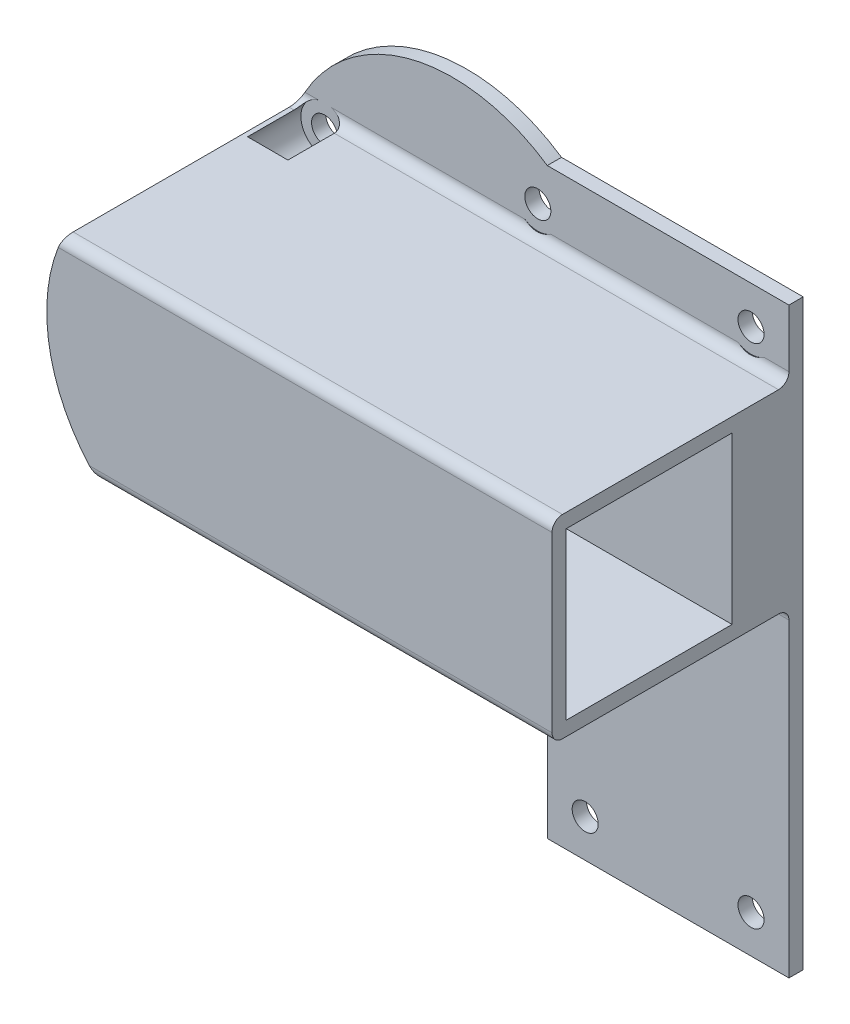
SolidWorks part; units mm, degrees
ref_plane "Front Plane" through (0, 0, 0) normal (0, 0, 1) x (1, 0, 0)
ref_plane "Top Plane" through (0, 0, 0) normal (0, 1, 0) x (1, 0, 0)
ref_plane "Right Plane" through (0, 0, 0) normal (1, 0, 0) x (0, 0, -1)
sketch "Sketch1" plane through (0, 0, 0) normal (0, 0, 1) x (1, 0, 0)
  line L0 (-35, -107) -> (0, -107) construction
  line L1 (-90, -9) -> (-90, -34) construction
  line L5 (8, 8) -> (-43, 8)
  line L6 (8, 8) -> (8, -115)
  line L7 (8, -115) -> (-43, -115)
  line L8 (-43, 8) -> (-43, -1.8875)
  line L9 (-90, -21.5) -> (-43, -21.5) construction
  line L10 (-43, -51) -> (-43, -115)
  circle A0 centre (-90, -34) radius 2.75
  circle A1 centre (-90, -9) radius 2.75
  circle A2 centre (-45, 0) radius 2.75
  circle A3 centre (0, 0) radius 2.75
  circle A4 centre (0, -107) radius 2.75
  circle A5 centre (-35, -107) radius 2.75
  arc A6 (-43, 8) -> (-43, -51) centre (-63, -21.5) ccw
  point P0 (0, 0)
  point P1 (-45, 0)
  point P3 (-90, -9)
  point P5 (-35, -107)
  point P6 (0, -107)
  point P7 (-90, -34)
  point P9 (-63, -21.5)
  dimension "D7" = 5.5
  dimension "D1" = 45
  dimension "D2" = 45
  dimension "D3" = 9
  dimension "D4" = 25
  dimension "D5" = 107
  dimension "D6" = 35
  dimension "D8" = 8
  dimension "D9" = 8
  dimension "D10" = 8
  dimension "D11" = 8
  dimension "D12" = 63
extrude "Boss-Extrude1" add sketch "Sketch1" along normal blind 3 contours A6 L10 L7 L6 L5 A2 A0 A1 A3 A4 A5 region at (-34.9713, -42.3703, 0)
sketch "Sketch4" plane through (0, 0, 3) normal (0, 0, 1) x (1, 0, 0)
  line L0 (-45, -2.75) -> (-45, -6.375) construction
  line L1 (-43, -51) -> (-43, -47.375) construction
  line L2 (8, 8) -> (8, -115) construction
  line L10 (-98.6406, -47.375) -> (8, -47.375)
  line L11 (-98.6406, -47.375) -> (-98.6406, -6.375)
  line L12 (-98.6406, -6.375) -> (8, -6.375)
  line L13 (8, -47.375) -> (8, -6.375)
  line L14 (-98.6406, -47.375) -> (8, -6.375) construction
  line L15 (-98.6406, -6.375) -> (8, -47.375) construction
  arc A1 (-43, 8) -> (-43, -51) centre (-63, -21.5) ccw construction
  circle A3 centre (-45, 0) radius 2.75 construction
  point P17 (-45.3203, -26.875)
  circle M9 centre (-90, -34) radius 2.75
  circle M10 centre (-90, -9) radius 2.75
  arc M15 (-43, 8) -> (-43, -51) centre (-63, -21.5) ccw
  line M18 (8, -115) -> (8, 8)
  dimension "D1" = 41
extrude "Boss-Extrude3" add sketch "Sketch4" along normal blind 50 contours L12 L10 M15 M18 M10 M9 | L12 M10 | M9 region at (-43.5545, -26.7001, 3) region at (-90, -9.0155, 3) region at (-90, -34, 3)
sketch "Sketch5" plane through (8, 0, 0) normal (1, 0, 0) x (0, 0, -1)
  line L1 (-50, -9.375) -> (-15, -9.375)
  line L2 (-50, -9.375) -> (-50, -44.375)
  line L3 (-50, -44.375) -> (-15, -44.375)
  line L4 (-15, -9.375) -> (-15, -44.375)
  line L6 (-53, -47.375) -> (-53, -6.375) construction
  line L7 (-53, -6.375) -> (-3, -6.375) construction
  dimension "D1" = 3
  dimension "D2" = 3
  dimension "D3" = 35
  dimension "D4" = 35
extrude "Cut-Extrude1" cut sketch "Sketch5" against normal through all
fillet "Fillet1" radius 2.2 4 edges at (-39.7549, -47.375, 3) (-39.7549, -47.375, 53) (-40.5902, -6.375, 3) (-43.636, -6.375, 53)
sketch "Sketch6" plane through (0, 0, 0) normal (0, 0, -1) x (-1, 0, 0)
  circle A0 centre (45, 0) radius 5
  circle A1 centre (45, 0) radius 5
  circle A2 centre (90, -9) radius 5
  circle A3 centre (90, -34) radius 5
  circle A4 centre (0, 0) radius 5
  point P0 (90, -9)
  circle M1 centre (45, 0) radius 2.75
  circle M4 centre (0, 0) radius 2.75
  dimension "D1" = 10
extrude "Cut-Extrude3" cut sketch "Sketch6" against normal blind 12 from offset 3 contours A4 M4 | A0 M1 | A2 | A3 region at (-40.1414, 0, 0) region at (4.8586, 0, 0) offset against normal yes
